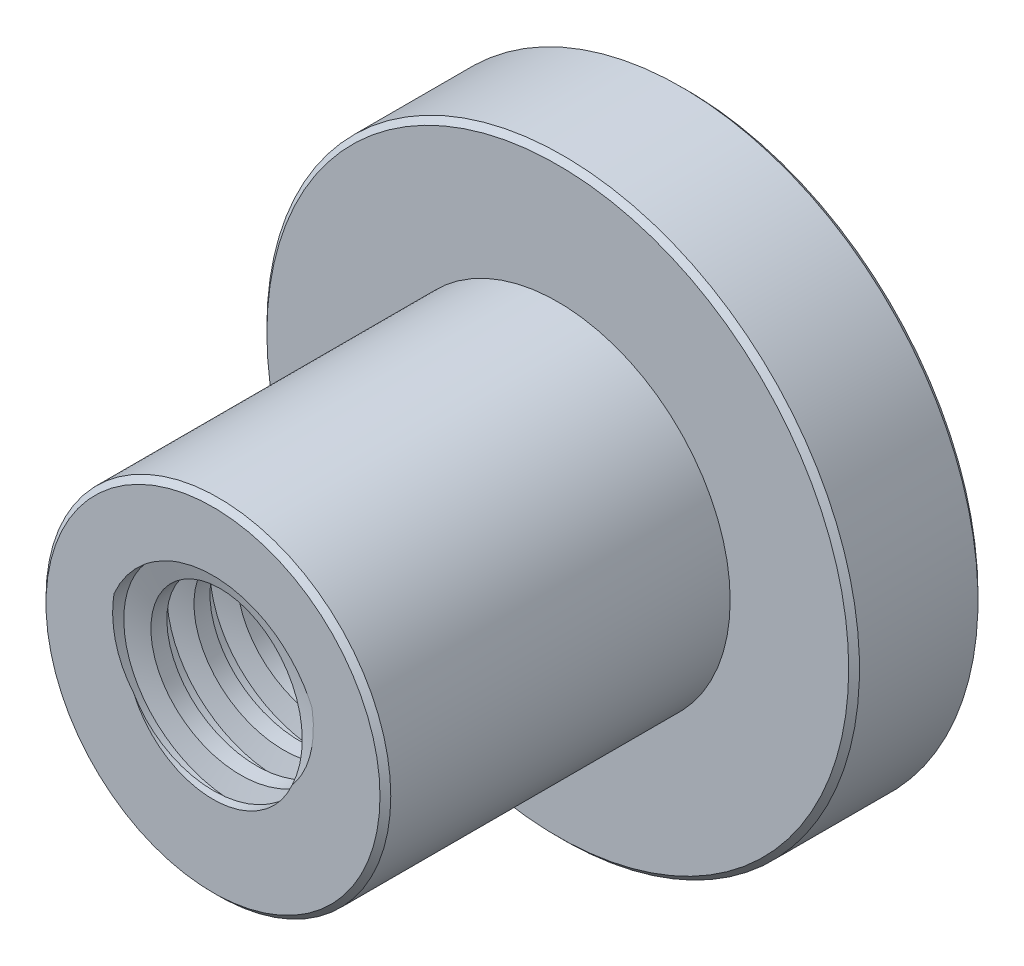
SolidWorks part; units mm, degrees
ref_plane "Front Plane" through (0, 0, 0) normal (0, 0, 1) x (1, 0, 0)
ref_plane "Top Plane" through (0, 0, 0) normal (0, 1, 0) x (1, 0, 0)
ref_plane "Right Plane" through (0, 0, 0) normal (1, 0, 0) x (0, 0, -1)
sketch "Sketch1" plane through (0, 0, 0) normal (0, 0, 1) x (1, 0, 0)
  circle A0 centre (0, 0) radius 8
  circle A1 centre (0, 0) radius 16
  dimension "D1" = 16
  dimension "D2" = 32
extrude "Boss-Extrude1" add sketch "Sketch1" along normal blind 32
sketch "Sketch2" plane through (0, 0, 0) normal (0, 0, -1) x (-1, 0, 0)
  circle A0 centre (0, 0) radius 8 construction
  circle A1 centre (0, 0) radius 8
  circle A2 centre (0, 0) radius 27.5
  dimension "D1" = 55
extrude "Boss-Extrude2" add sketch "Sketch2" along normal blind 12
chamfer "Chamfer1" distance 0.5 angle 45 3 edges at (-27.5, 0, -12) (-27.5, 0, 0) (16, 0, 32)
chamfer "Chamfer2" distance 1 angle 45 1 edges at (-8, 0, -12)
sketch "Sketch3" plane through (0, 0, 32) normal (0, 0, 1) x (1, 0, 0)
  circle A0 centre (0, 0) radius 8 construction
  circle A1 centre (0, 0) radius 8
curve "Helix/Spiral1" pitch 4 height 44 radius 8 left hand yes centre (0, 0, 32) axis (0, 0, -1) start towards (-1, 0, 0)
sketch "Sketch4" plane through (0, 0, 0) normal (1, 0, 0) x (0, 0, -1)
  line L0 (-0.7414, 10) -> (-1.2586, 8)
  line L1 (-1.2586, 8) -> (1.2586, 8)
  line L2 (1.2586, 8) -> (0.7414, 10)
  line L3 (-0.7414, 10) -> (0.7414, 10)
  line L4 (-3.9656, 9) -> (6.7612, 9) construction
  line L5 (0, 13.2602) -> (0, 7.1313) construction
  line L7 (0, 55) -> (0, -55) construction
  line L8 (55, 0) -> (-55, 0) construction
  spline S0 degree 3 poles (-32, 0) (-31.9172, -1.0405) (-31.7498, -3.1442) (-31.5001, -5.8033) (-31.25, -7.5837) (-31, -8.2082) (-30.75, -7.5835) (-30.5, -5.8041) (-30.1667, -2.2535) (-29.8333, 2.2535) (-29.5, 5.8041) (-29.25, 7.5835) (-29, 8.2083) (-28.75, 7.5835) (-28.5, 5.8041) (-28.1667, 2.2535) (-27.8333, -2.2535) (-27.5, -5.8041) (-27.25, -7.5835) (-27, -8.2083) (-26.75, -7.5835) (-26.5, -5.8041) (-26.1667, -2.2535) (-25.8333, 2.2535) (-25.5, 5.8041) (-25.25, 7.5835) (-25, 8.2083) (-24.75, 7.5835) (-24.5, 5.8041) (-24.1667, 2.2535) (-23.8333, -2.2535) (-23.5, -5.8041) (-23.25, -7.5835) (-23, -8.2083) (-22.75, -7.5835) (-22.5, -5.8041) (-22.1667, -2.2535) (-21.8333, 2.2535) (-21.5, 5.8041) (-21.25, 7.5835) (-21, 8.2083) (-20.75, 7.5835) (-20.5, 5.8041) (-20.1667, 2.2535) (-19.8333, -2.2535) (-19.5, -5.8041) (-19.25, -7.5835) (-19, -8.2083) (-18.75, -7.5835) (-18.5, -5.8041) (-18.1667, -2.2535) (-17.8333, 2.2535) (-17.5, 5.8041) (-17.25, 7.5835) (-17, 8.2083) (-16.75, 7.5835) (-16.5, 5.8041) (-16.1667, 2.2535) (-15.8333, -2.2535) (-15.5, -5.8041) (-15.25, -7.5835) (-15, -8.2083) (-14.75, -7.5835) (-14.5, -5.8041) (-14.1667, -2.2535) (-13.8333, 2.2535) (-13.5, 5.8041) (-13.25, 7.5835) (-13, 8.2083) (-12.75, 7.5835) (-12.5, 5.8041) (-12.1667, 2.2535) (-11.8333, -2.2535) (-11.5, -5.8041) (-11.25, -7.5835) (-11, -8.2083) (-10.75, -7.5835) (-10.5, -5.8041) (-10.1667, -2.2535) (-9.8333, 2.2535) (-9.5, 5.8041) (-9.25, 7.5835) (-9, 8.2083) (-8.75, 7.5835) (-8.5, 5.8041) (-8.1667, 2.2535) (-7.8333, -2.2535) (-7.5, -5.8041) (-7.25, -7.5835) (-7, -8.2083) (-6.75, -7.5835) (-6.5, -5.8041) (-6.1667, -2.2535) (-5.8333, 2.2535) (-5.5, 5.8041) (-5.25, 7.5835) (-5, 8.2083) (-4.75, 7.5835) (-4.5, 5.8041) (-4.1667, 2.2535) (-3.8333, -2.2535) (-3.5, -5.8041) (-3.25, -7.5835) (-3, -8.2083) (-2.75, -7.5835) (-2.5, -5.8041) (-2.1667, -2.2535) (-1.8333, 2.2535) (-1.5, 5.8041) (-1.25, 7.5835) (-1, 8.2083) (-0.75, 7.5835) (-0.5, 5.8041) (-0.1667, 2.2535) (0.1667, -2.2535) (0.5, -5.8041) (0.75, -7.5835) (1, -8.2083) (1.25, -7.5835) (1.5, -5.8041) (1.8333, -2.2535) (2.1667, 2.2535) (2.5, 5.8041) (2.75, 7.5835) (3, 8.2083) (3.25, 7.5835) (3.5, 5.8041) (3.8333, 2.2535) (4.1667, -2.2535) (4.5, -5.8041) (4.75, -7.5835) (5, -8.2083) (5.25, -7.5835) (5.5, -5.8041) (5.8333, -2.2535) (6.1667, 2.2535) (6.5, 5.8041) (6.75, 7.5835) (7, 8.2083) (7.25, 7.5835) (7.5, 5.8041) (7.8333, 2.2535) (8.1667, -2.2535) (8.5, -5.8041) (8.75, -7.5835) (9, -8.2083) (9.25, -7.5835) (9.5, -5.8041) (9.8333, -2.2535) (10.1667, 2.2535) (10.5, 5.8041) (10.75, 7.5835) (11, 8.2082) (11.25, 7.5837) (11.5001, 5.8033) (11.7498, 3.1442) (11.9172, 1.0405) (12, 0) knots 0 0 0 0 0.005682 0.011364 0.017045 0.022727 0.028409 0.034091 0.039773 0.051136 0.056818 0.0625 0.068182 0.073864 0.079545 0.085227 0.096591 0.102273 0.107955 0.113636 0.119318 0.125 0.130682 0.142045 0.147727 0.153409 0.159091 0.164773 0.170455 0.176136 0.1875 0.193182 0.198864 0.204545 0.210227 0.215909 0.221591 0.232955 0.238636 0.244318 0.25 0.255682 0.261364 0.267045 0.278409 0.284091 0.289773 0.295455 0.301136 0.306818 0.3125 0.323864 0.329545 0.335227 0.340909 0.346591 0.352273 0.357955 0.369318 0.375 0.380682 0.386364 0.392045 0.397727 0.403409 0.414773 0.420455 0.426136 0.431818 0.4375 0.443182 0.448864 0.460227 0.465909 0.471591 0.477273 0.482955 0.488636 0.494318 0.505682 0.511364 0.517045 0.522727 0.528409 0.534091 0.539773 0.551136 0.556818 0.5625 0.568182 0.573864 0.579545 0.585227 0.596591 0.602273 0.607955 0.613636 0.619318 0.625 0.630682 0.642045 0.647727 0.653409 0.659091 0.664773 0.670455 0.676136 0.6875 0.693182 0.698864 0.704545 0.710227 0.715909 0.721591 0.732955 0.738636 0.744318 0.75 0.755682 0.761364 0.767045 0.778409 0.784091 0.789773 0.795455 0.801136 0.806818 0.8125 0.823864 0.829545 0.835227 0.840909 0.846591 0.852273 0.857955 0.869318 0.875 0.880682 0.886364 0.892045 0.897727 0.903409 0.914773 0.920455 0.926136 0.931818 0.9375 0.943182 0.948864 0.960227 0.965909 0.971591 0.977273 0.982955 0.988636 0.994318 1 1 1 1 construction
  point P8 (-1, 9)
  point P9 (1, 9)
  dimension "D2" = 2
  dimension "D1" = 29
  dimension "D3" = 10
sweep "Cut-Sweep1" cut profiles "Sketch4" path "Helix/Spiral1" align with end faces yes
sketch "Sketch5" plane through (0, 0, 0) normal (0, 0, 1) x (1, 0, 0)
  circle A0 centre (0, 0) radius 22.8622 construction
equation "\"d\"= 20mm"
equation "\"p\"= 4mm"
equation "\"dm\"= \"d\" - \"p\" / 2"
equation "\"dr\"= \"d\" - \"p\""
equation "\"D1@Sketch1\"=\"dr\""
equation "\"D2@Sketch4\"=\"p\"/2"
equation "\"D3@Sketch4\"=\"d\"/2"
